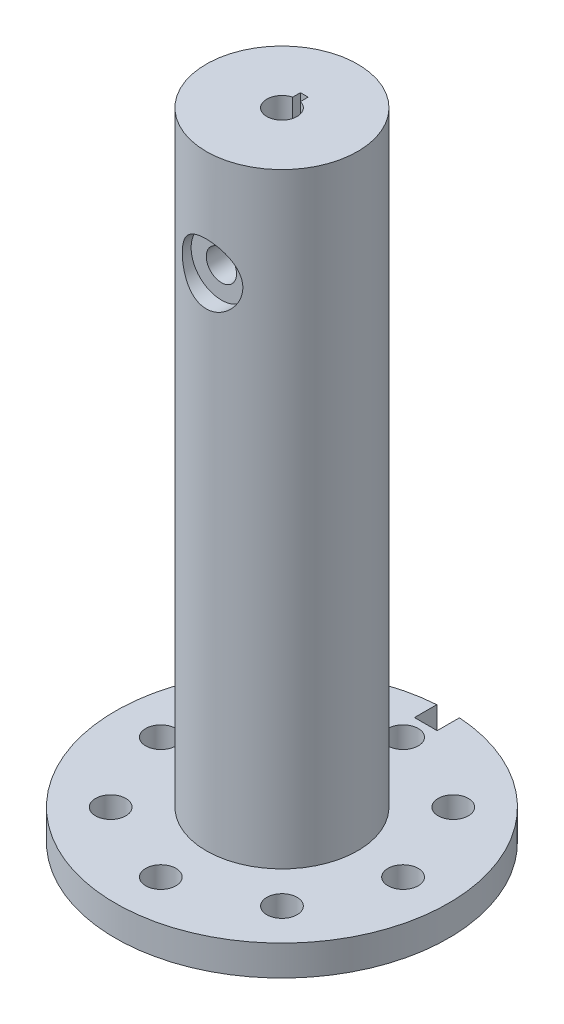
SolidWorks part; units mm, degrees
ref_plane "Front Plane" through (0, 0, 0) normal (0, 0, 1) x (1, 0, 0)
ref_plane "Top Plane" through (0, 0, 0) normal (0, 1, 0) x (1, 0, 0)
ref_plane "Right Plane" through (0, 0, 0) normal (1, 0, 0) x (0, 0, -1)
sketch "Sketch1" plane through (0, 0, 0) normal (0, 1, 0) x (1, 0, 0)
  circle A0 centre (0, 0) radius 11
  circle A1 centre (0, 8) radius 1
  circle A2 centre (5.6569, 5.6569) radius 1
  circle A3 centre (8, 0) radius 1
  circle A4 centre (5.6569, -5.6569) radius 1
  circle A5 centre (0, -8) radius 1
  circle A6 centre (-5.6569, -5.6569) radius 1
  circle A7 centre (-8, 0) radius 1
  circle A8 centre (-5.6569, 5.6569) radius 1
  point P22 (0, 0)
  dimension "D1" = 22
  dimension "D2" = 2
  dimension "D6" = 8
  dimension "D3" = 8
  dimension "D5" = 8
  dimension "D4" = 8
extrude "Boss-Extrude1" add sketch "Sketch1" along normal blind 2
sketch "Sketch2" plane through (0, 2, 0) normal (0, 1, 0) x (1, 0, 0)
  circle A0 centre (0, 0) radius 3.5
  dimension "D1" = 7
extrude "Cut-Extrude1" cut sketch "Sketch2" against normal through all
ref_plane "Plane1" through (0, 0, 0) normal (0, 1, 0) x (1, 0, 0)
sketch "Sketch3" plane through (0, 0, 0) normal (0, 1, 0) x (1, 0, 0)
  circle A0 centre (0, 0) radius 5
  circle A1 centre (0, 0) radius 11
  dimension "D1" = 10
  dimension "D2" = 22
sketch "Sketch4" plane through (0, 2, 0) normal (0, 1, 0) x (1, 0, 0)
  line L1 (-0.75, 12.5) -> (0.75, 12.5)
  line L2 (-0.75, 12.5) -> (-0.75, 9.5)
  line L3 (-0.75, 9.5) -> (0.75, 9.5)
  line L4 (0.75, 12.5) -> (0.75, 9.5)
  line L5 (-0.75, 12.5) -> (0.75, 9.5) construction
  line L6 (-0.75, 9.5) -> (0.75, 12.5) construction
  circle A0 centre (0, 0) radius 11 construction
  point P0 (0, 11)
  dimension "D1" = 1.5
  dimension "D2" = 3
extrude "Cut-Extrude3" cut sketch "Sketch4" against normal blind 4
sketch "Sketch5" plane through (0, 2, 0) normal (0, 1, 0) x (1, 0, 0)
  circle A0 centre (0, 0) radius 3.5
  circle A1 centre (0, 0) radius 5
  dimension "D1" = 7
  dimension "D2" = 10
extrude "Boss-Extrude2" add sketch "Sketch5" along normal blind 20 contours A1 | A0
sketch "Sketch6" plane through (0, 22, 0) normal (0, 1, 0) x (1, 0, 0)
  line L0 (-0.255, 0.9669) -> (0.255, 0.9669)
  line L1 (-0.255, 0.9669) -> (-0.255, 1.4769)
  line L2 (0.255, 0.9669) -> (0.255, 1.4769)
  line L3 (-0.255, 1.4769) -> (0.255, 1.4769)
  circle A0 centre (0, 0) radius 1
  circle A1 centre (0, 0) radius 3.5
  circle A2 centre (0, 0) radius 5
  circle M4 centre (0, 0) radius 5
  circle M5 centre (0, 0) radius 3.5
  dimension "D1" = 2
  dimension "D4" = 7
  dimension "D5" = 10
  dimension "D2" = 0.51
  dimension "D3" = 0.51
extrude "Boss-Extrude3" add sketch "Sketch6" along normal blind 20 contours A0 L1 L3 L2 M5 | M4 M5 region at (-3.401, 22, 0) region at (-4.8586, 22, 0)
sketch "Sketch7" plane through (0, 0, 0) normal (0, 0, 1) x (1, 0, 0)
  line L0 (11, 0) -> (-11, 0) construction
  circle A0 centre (0, 35) radius 1
  dimension "D1" = 2
  dimension "D2" = 35
extrude "Cut-Extrude4" cut sketch "Sketch7" against normal blind 1 and the other way blind 5
ref_plane "Plane2" through (0, 0, 5) normal (0, 0, 1) x (1, 0, 0)
sketch "Sketch8" plane through (0, 0, 5) normal (0, 0, 1) x (1, 0, 0)
  circle A0 centre (0, 35) radius 2
  dimension "D1" = 4
extrude "Cut-Extrude5" cut sketch "Sketch8" against normal blind 1
